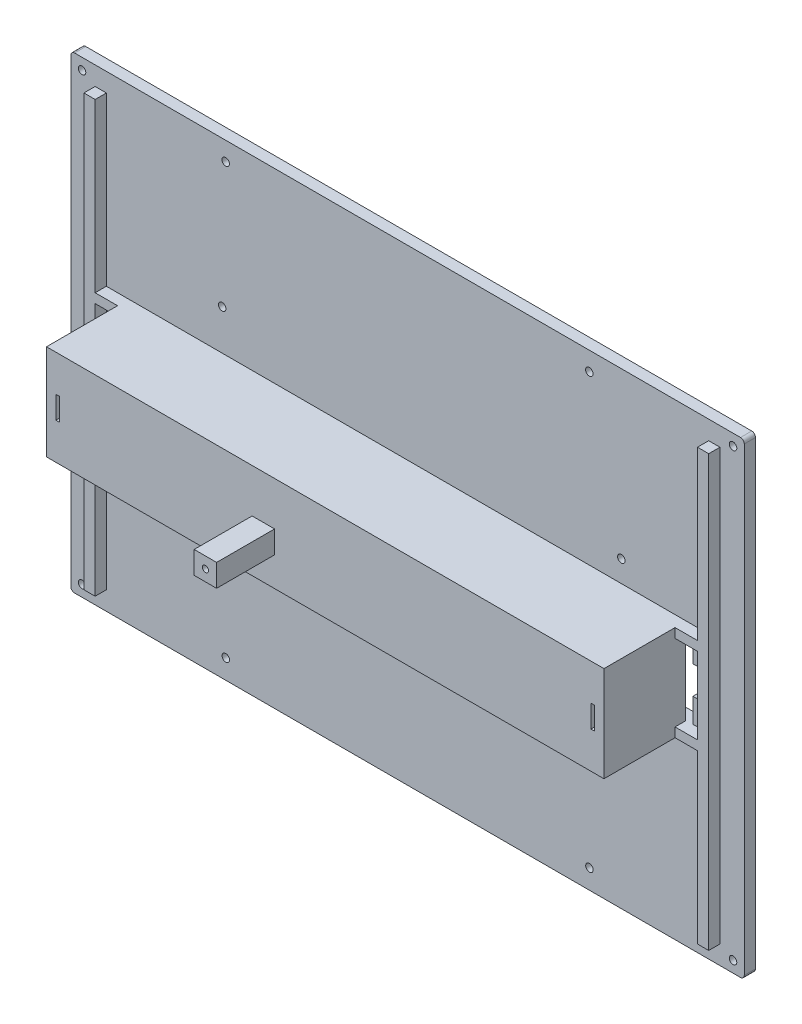
SolidWorks part; units mm, degrees
ref_plane "前视基准面" through (0, 0, 0) normal (0, 0, 1) x (1, 0, 0)
ref_plane "上视基准面" through (0, 0, 0) normal (0, 1, 0) x (1, 0, 0)
ref_plane "右视基准面" through (0, 0, 0) normal (1, 0, 0) x (0, 0, -1)
sketch "草图1" plane through (0, 0, 0) normal (0, 0, 1) x (1, 0, 0)
  line L1 (-90, 62.5) -> (90, 62.5)
  line L2 (-90, 62.5) -> (-90, -62.5)
  line L3 (-90, -62.5) -> (90, -62.5)
  line L4 (90, 62.5) -> (90, -62.5)
  line L5 (-90, 62.5) -> (90, -62.5) construction
  line L6 (-90, -62.5) -> (90, 62.5) construction
  point P0 (0, 0)
  dimension "D1" = 125
  dimension "D2" = 180
extrude "凸台-拉伸1" add sketch "草图1" along normal blind 3
sketch "草图7" plane through (0, 0, 0) normal (0, 0, -1) x (-1, 0, 0)
  line L1 (-72, 10.25) -> (72, 10.25)
  line L2 (-72, 10.25) -> (-72, -10.25)
  line L3 (-72, -10.25) -> (72, -10.25)
  line L4 (72, 10.25) -> (72, -10.25)
  line L5 (0, 0) -> (72.729, 0) construction
  line L8 (0, 0) -> (0, -50.9103) construction
  dimension "D1" = 20.5
  dimension "D2" = 144
extrude "电池位切除-拉伸3" cut sketch "草图7" against normal up to next
sketch "草图8" plane through (0, 0, 3) normal (0, 0, 1) x (1, 0, 0)
  line L12 (72, 10.25) -> (72, -10.25) construction
  line L13 (-74.5, 12.75) -> (74.5, 12.75)
  line L14 (-74.5, 12.75) -> (-74.5, -12.75)
  line L15 (-74.5, -12.75) -> (74.5, -12.75)
  line L16 (74.5, 12.75) -> (74.5, -12.75)
  line L17 (-72, -10.25) -> (-72, 10.25) construction
  line L18 (-72, 10.25) -> (72, 10.25) construction
  line L19 (72, -10.25) -> (-72, -10.25) construction
  line L20 (-72, 10.25) -> (72, 10.25)
  line L21 (72, -10.25) -> (-72, -10.25)
  line L22 (72, 10.25) -> (72, -10.25)
  line L23 (-72, -10.25) -> (-72, 10.25) construction
  line L24 (-72, -10.25) -> (-72, 10.25)
  dimension "D1" = 2.5
  dimension "D2" = 2.5
  dimension "D3" = 2.5
  dimension "D4" = 2.5
extrude "凸台-拉伸2" add sketch "草图8" along normal blind 22
sketch "草图9" plane through (0, 0, 25) normal (0, 0, 1) x (1, 0, 0)
  line L0 (74.5, 12.75) -> (-74.5, 12.75) construction
  line L5 (74.5, 12.75) -> (-74.5, 12.75)
  line L6 (-74.5, -12.75) -> (74.5, -12.75) construction
  line L7 (-74.5, -12.75) -> (74.5, -12.75)
  line L8 (74.5, -12.75) -> (74.5, 12.75) construction
  line L9 (74.5, -12.75) -> (74.5, 12.75)
  line L10 (-74.5, 12.75) -> (-74.5, -12.75) construction
  line L11 (-74.5, 12.75) -> (-74.5, -12.75)
extrude "凸台-拉伸3" add sketch "草图9" against normal blind 2.5
sketch "草图4" plane through (0, 0, 0) normal (0, 0, -1) x (-1, 0, 0)
  line L0 (72, -10.25) -> (72, 10.25) construction
  line L5 (72, 0) -> (84.6307, 0) construction
  line L10 (83.2374, -53.4277) -> (79.3374, -53.4277) construction
  line L11 (83.2374, -49.6277) -> (83.2374, -53.4277) construction
  line L12 (79.3374, -49.6277) -> (83.2374, -49.6277) construction
  line L29 (72, -4) -> (74.5, -4)
  line L30 (74.5, -4) -> (74.5, 4)
  line L31 (74.5, 4) -> (72, 4)
  line L32 (72, 4) -> (72, -4)
  dimension "D1" = 8
  dimension "D2" = 2.5
extrude "切除-拉伸2" cut sketch "草图4" against normal blind 2 from offset 1.5 offset against normal yes
sketch "草图10" plane through (0, 0, 25) normal (0, 0, 1) x (1, 0, 0)
  line L0 (-16.5366, -1.9347) -> (8.5541, -1.9347) construction
  line L2 (-19.5366, 1.0653) -> (-19.5366, -4.9347)
  line L4 (-13.5366, 1.0653) -> (-13.5366, -4.9347)
  line L5 (-16.5366, -1.9347) -> (-16.5366, 4.0653) construction
  line L6 (0, 0) -> (60.8594, 0) construction
  line L7 (0, 0) -> (0, 60.5) construction
  line L8 (75, 60.5) -> (-75, 60.5) construction
  line L9 (-19.5366, 1.0653) -> (-13.5366, 1.0653)
  line L10 (-19.5366, -4.9347) -> (-13.5366, -4.9347)
  circle A0 centre (-16.5366, -1.9347) radius 0.825
  dimension "D2" = 1.65
  dimension "D1" = 6
extrude "凸台-拉伸4" add sketch "草图10" along normal up to surface (15.5 mm away)
sketch "草图11" plane through (0, 0, 0) normal (0, 0, -1) x (-1, 0, 0)
  circle A0 centre (-48.6147, -57.3) radius 1 construction
  circle A1 centre (-49.55, -23.3) radius 1 construction
  circle A2 centre (57.15, -18.3) radius 1 construction
  circle A3 centre (48.5747, -57.3) radius 1 construction
  circle A4 centre (87, 59.5) radius 1
  circle A5 centre (48.6147, 57.5) radius 1 construction
  circle A6 centre (-57.15, 18.5) radius 1 construction
  circle A7 centre (-48.5747, 57.5) radius 1 construction
  circle A8 centre (-48.6147, -57.3) radius 1
  circle A9 centre (-49.55, -23.3) radius 1
  circle A10 centre (57.15, -18.3) radius 1
  circle A11 centre (48.5747, -57.3) radius 1
  circle A13 centre (48.6147, 57.5) radius 1
  circle A14 centre (-57.15, 18.5) radius 1
  circle A15 centre (-48.5747, 57.5) radius 1
  circle A16 centre (49.55, 23.5) radius 1 construction
  circle A17 centre (49.55, 23.5) radius 1
  circle A18 centre (87, -59.5) radius 1
  circle A19 centre (-87, -59.5) radius 1
  circle A20 centre (-87, 59.5) radius 1
  dimension "D1" = 2
  dimension "D2" = 2
  dimension "D3" = 2
  dimension "D4" = 2
extrude "固定螺丝切除-拉伸3" cut sketch "草图11" against normal up to next
sketch "草图12" plane through (0, 0, 0) normal (0, 0, -1) x (-1, 0, 0)
  circle A0 centre (-48.5747, 57.5) radius 2
  circle A1 centre (-57.15, 18.5) radius 2
  circle A2 centre (-49.55, -23.3) radius 2
  circle A3 centre (-48.6147, -57.3) radius 2
  circle A4 centre (48.5747, -57.3) radius 2
  circle A5 centre (57.15, -18.3) radius 2
  circle A7 centre (-87, 59.5) radius 2
  circle A8 centre (48.6147, 57.5) radius 2
  circle A9 centre (49.55, 23.5) radius 2
  circle A10 centre (-87, -59.5) radius 2
  circle A11 centre (87, -59.5) radius 2
  circle A12 centre (87, 59.5) radius 2
  dimension "D1" = 4
  dimension "D2" = 4
  dimension "D3" = 4
  dimension "D4" = 4
  dimension "D5" = 4
extrude "固定螺丝凹陷切除-拉伸4" cut sketch "草图12" against normal blind 1.2
fillet "圆角1" radius 1 4 edges at (90, -62.5, 1.5) (-90, -62.5, 1.5) (-90, 62.5, 1.5) (90, 62.5, 1.5)
sketch "草图13" plane through (0, 0, 25) normal (0, 0, 1) x (1, 0, 0)
  line L0 (72, 10.25) -> (72, -10.25) construction
  line L1 (72, 3) -> (71, 3)
  line L2 (72, 3) -> (72, -3)
  line L3 (72, -3) -> (71, -3)
  line L4 (71, 3) -> (71, -3)
  line L5 (-72, -10.25) -> (-72, 10.25) construction
  line L6 (-71, 3) -> (-72, 3)
  line L7 (-71, 3) -> (-71, -3)
  line L8 (-71, -3) -> (-72, -3)
  line L9 (-72, 3) -> (-72, -3)
  line L10 (72, 0) -> (59.7453, 0) construction
  dimension "D1" = 1
  dimension "D2" = 6
  dimension "D3" = 1
  dimension "D4" = 6
extrude "切除-拉伸3" cut sketch "草图13" against normal up to next
sketch "草图14" plane through (0, 0, 22.5) normal (0, 0, -1) x (-1, 0, 0)
  line L0 (72, 10.25) -> (-72, 10.25) construction
  line L1 (-71, 10.25) -> (-69, 10.25)
  line L2 (-71, 10.25) -> (-71, 5.25)
  line L3 (-71, 5.25) -> (-69, 5.25)
  line L4 (-69, 10.25) -> (-69, 5.25)
  line L5 (-72, 0) -> (-60.8543, 0) construction
  line L6 (-72, 10.25) -> (-72, -10.25) construction
  line L7 (72, 0) -> (63.4917, 0) construction
  line L8 (69, 10.25) -> (71, 10.25)
  line L9 (69, 10.25) -> (69, 5.75)
  line L10 (69, 5.75) -> (71, 5.75)
  line L11 (71, 10.25) -> (71, 5.75)
  line L12 (72, -10.25) -> (72, 10.25) construction
  line L13 (71, -10.25) -> (71, -5.75)
  line L14 (69, -5.75) -> (71, -5.75)
  line L15 (69, -10.25) -> (69, -5.75)
  line L16 (69, -10.25) -> (71, -10.25)
  line L17 (-69, -10.25) -> (-69, -5.25)
  line L18 (-71, -5.25) -> (-69, -5.25)
  line L19 (-71, -10.25) -> (-71, -5.25)
  line L20 (-71, -10.25) -> (-69, -10.25)
  dimension "D1" = 1
  dimension "D2" = 2
  dimension "D3" = 4.5
  dimension "D4" = 1
  dimension "D5" = 2
  dimension "D6" = 5
extrude "凸台-拉伸5" add sketch "草图14" along normal blind 16
sketch "草图15" plane through (0, 0, 0) normal (0, 0, -1) x (-1, 0, 0)
  line L7 (-72, -10.25) -> (72, -10.25) construction
  line L8 (-76.3, 10.25) -> (-72, 10.25)
  line L9 (-76.3, 10.25) -> (-76.3, 3.75)
  line L10 (-76.3, -10.25) -> (-72, -10.25)
  line L11 (-72, 10.25) -> (-72, -10.25)
  line L12 (-76.3, 3.75) -> (-79.3365, 3.75)
  line L14 (-76.3, -3.75) -> (-79.3365, -3.75)
  line L15 (-79.3365, 3.75) -> (-79.3365, -3.75)
  line L16 (72, 10.25) -> (-72, 10.25) construction
  line L17 (-76.3, -3.75) -> (-76.3, -10.25)
  line L18 (-76.1, -10.05) -> (-76.1, 10.05) construction
  line L19 (-79.2365, 3.5) -> (-79.2365, -3.5) construction
  dimension "D1" = 6.5
  dimension "D2" = 6.5
  dimension "D3" = 0.2
  dimension "D4" = 0.1
extrude "切除-拉伸6" cut sketch "草图15" against normal blind 3.2
sketch "草图17" plane through (0, 0, 0) normal (0, 0, -1) x (-1, 0, 0)
  line L0 (-76.3, 3.75) -> (-79.3365, 3.75) construction
  line L1 (-81.8365, 3.75) -> (-79.3365, 3.75)
  line L2 (-81.8365, 3.75) -> (-81.8365, -3.75)
  line L3 (-81.8365, -3.75) -> (-79.3365, -3.75)
  line L4 (-79.3365, 3.75) -> (-79.3365, -3.75)
  dimension "D1" = 2.5
extrude "切除-拉伸7" cut sketch "草图17" against normal blind 1.5
fillet "圆角2" radius 0.25 26 edges at (-71, 10.25, 14.5) (-69, 10.25, 14.5) (-69, -10.25, 14.5) (-71, -10.25, 14.5) (71, -10.25, 14.5) (69, -10.25, 14.5) (69, 10.25, 14.5) (71, 10.25, 14.5) (-70, 10.25, 6.5) (-71, 8, 6.5) (-70, 5.75, 6.5) (-69, 8, 6.5) (-69, -8, 6.5) (-70, -5.75, 6.5) (-71, -8, 6.5) (-70, -10.25, 6.5) (71, -7.75, 6.5) (70, -5.25, 6.5) (69, -7.75, 6.5) (70, -10.25, 6.5) (70, 10.25, 6.5) (69, 7.75, 6.5) (70, 5.25, 6.5) (71, 7.75, 6.5) (79.3365, 0, 3) (81.8365, 0, 0)
sketch "草图18" plane through (0, 0, 3) normal (0, 0, 1) x (1, 0, 0)
  line L0 (0, 0) -> (0, 49.5083) construction
  line L1 (-83.5, 57.5) -> (-80.5, 57.5)
  line L2 (-83.5, 57.5) -> (-83.5, -57.5)
  line L3 (-83.5, -57.5) -> (-80.5, -57.5)
  line L4 (-80.5, 57.5) -> (-80.5, 12.75)
  line L5 (89, 62.5) -> (-89, 62.5) construction
  line L6 (-89, -62.5) -> (89, -62.5) construction
  line L7 (-74.5, 12.75) -> (-74.5, -12.75) construction
  line L12 (-80.5, 10.25) -> (-80.5, -10.25)
  line L13 (-74.5, 12.75) -> (-80.5, 12.75)
  line L14 (-74.5, 12.75) -> (-74.5, 10.25)
  line L15 (-74.5, 10.25) -> (-80.5, 10.25)
  line L17 (-74.5, -12.75) -> (-80.5, -12.75)
  line L18 (-74.5, -12.75) -> (-74.5, -10.25)
  line L19 (-74.5, -10.25) -> (-80.5, -10.25)
  line L21 (-80.5, -12.75) -> (-80.5, -57.5)
  line L22 (80.5, -12.75) -> (80.5, -57.5)
  line L23 (74.5, -10.25) -> (80.5, -10.25)
  line L24 (74.5, -12.75) -> (74.5, -10.25)
  line L25 (74.5, -12.75) -> (80.5, -12.75)
  line L26 (74.5, 10.25) -> (80.5, 10.25)
  line L27 (74.5, 12.75) -> (74.5, 10.25)
  line L28 (74.5, 12.75) -> (80.5, 12.75)
  line L29 (80.5, 10.25) -> (80.5, -10.25)
  line L30 (80.5, 57.5) -> (80.5, 12.75)
  line L31 (83.5, -57.5) -> (80.5, -57.5)
  line L32 (83.5, 57.5) -> (83.5, -57.5)
  line L33 (83.5, 57.5) -> (80.5, 57.5)
  dimension "D1" = 5
  dimension "D2" = 5
  dimension "D3" = 3
  dimension "D4" = 6
  dimension "D5" = 2.5
extrude "凸台-拉伸6" add sketch "草图18" along normal blind 3
